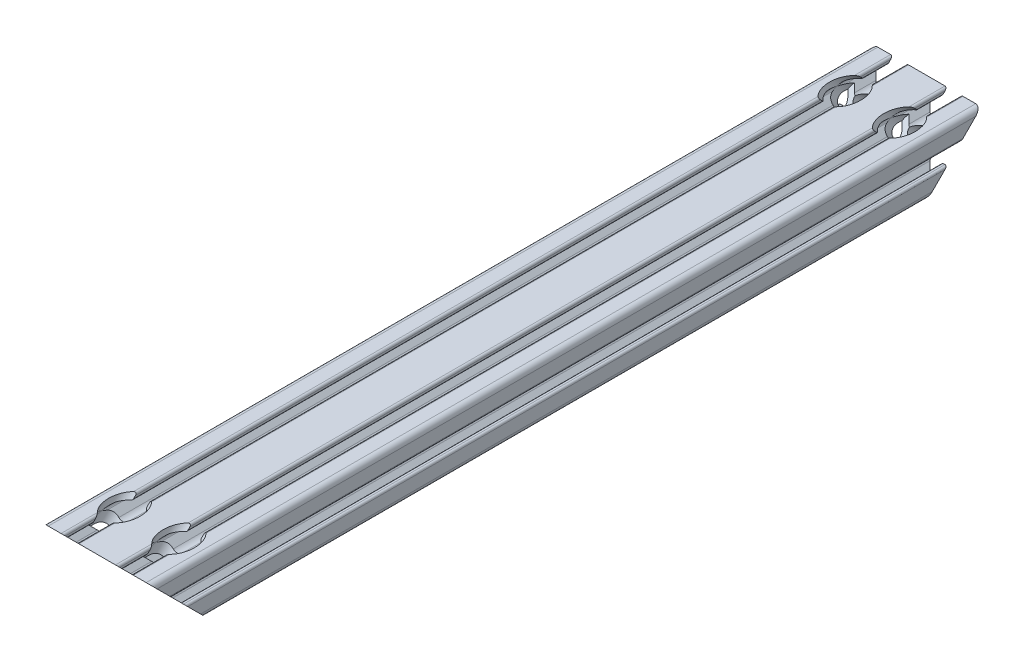
SolidWorks part; units mm, degrees
ref_plane "Front Plane" through (0, 0, 0) normal (0, 0, 1) x (1, 0, 0)
ref_plane "Top Plane" through (0, 0, 0) normal (0, 1, 0) x (1, 0, 0)
ref_plane "Right Plane" through (0, 0, 0) normal (1, 0, 0) x (0, 0, -1)
sketch "Sketch1" plane through (0, 0, 0) normal (0, 0, 1) x (1, 0, 0)
  line L2 (-19.9898, 7.9883) -> (-19.9898, 3.2893)
  line L3 (-17.9832, 9.9949) -> (-13.2842, 9.9949)
  line L4 (-12.4968, 9.2075) -> (-12.4968, 8.4963)
  line L5 (-12.8016, 8.1915) -> (-14.9098, 8.1915)
  line L6 (-15.5025, 6.7606) -> (-13.2477, 4.5058)
  line L7 (-16.7555, 5.5076) -> (-14.5007, 3.2528)
  line L8 (-18.1864, 4.9149) -> (-18.1864, 2.8067)
  line L9 (-18.4912, 2.5019) -> (-19.2024, 2.5019)
  line L11 (-11.1283, 3.6279) -> (-8.8615, 3.6279)
  line L12 (-13.6228, 1.1334) -> (-13.6228, -1.1334)
  line L13 (0, 9.9949) -> (-6.7056, 9.9949)
  line L14 (-7.493, 9.2075) -> (-7.493, 8.4963)
  line L15 (-7.1882, 8.1915) -> (-5.08, 8.1915)
  line L16 (-6.367, 1.1334) -> (-6.367, -1.1334)
  line L17 (-4.4873, 6.7606) -> (-6.7421, 4.5058)
  line L18 (-0.9396, 7.8023) -> (-5.4891, 3.2528)
  line L19 (-18.4912, -2.5019) -> (-19.2024, -2.5019)
  line L20 (-18.1864, -4.9149) -> (-18.1864, -2.8067)
  line L21 (-16.7555, -5.5076) -> (-14.5007, -3.2528)
  line L22 (-15.5025, -6.7606) -> (-13.2477, -4.5058)
  line L23 (-12.8016, -8.1915) -> (-14.9098, -8.1915)
  line L24 (-12.4968, -9.2075) -> (-12.4968, -8.4963)
  line L25 (-17.9832, -9.9949) -> (-13.2842, -9.9949)
  line L26 (-19.9898, -7.9883) -> (-19.9898, -3.2893)
  line L27 (0, -9.9949) -> (-6.7056, -9.9949)
  line L28 (-7.493, -9.2075) -> (-7.493, -8.4963)
  line L29 (-7.1882, -8.1915) -> (-5.08, -8.1915)
  line L30 (-4.4873, -6.7606) -> (-6.7421, -4.5058)
  line L31 (-0.9396, -7.8023) -> (-5.4891, -3.2528)
  line L32 (-11.1283, -3.6279) -> (-8.8615, -3.6279)
  line L34 (11.1283, -3.6279) -> (8.8615, -3.6279)
  line L35 (0.9396, -7.8023) -> (5.4891, -3.2528)
  line L36 (4.4873, -6.7606) -> (6.7421, -4.5058)
  line L37 (7.1882, -8.1915) -> (5.08, -8.1915)
  line L38 (7.493, -9.2075) -> (7.493, -8.4963)
  line L39 (0, -9.9949) -> (6.7056, -9.9949)
  line L40 (19.9898, -7.9883) -> (19.9898, -3.2893)
  line L41 (17.9832, -9.9949) -> (13.2842, -9.9949)
  line L42 (12.4968, -9.2075) -> (12.4968, -8.4963)
  line L43 (12.8016, -8.1915) -> (14.9098, -8.1915)
  line L44 (15.5025, -6.7606) -> (13.2477, -4.5058)
  line L45 (16.7555, -5.5076) -> (14.5007, -3.2528)
  line L46 (18.1864, -4.9149) -> (18.1864, -2.8067)
  line L47 (18.4912, -2.5019) -> (19.2024, -2.5019)
  line L48 (0.9396, 7.8023) -> (5.4891, 3.2528)
  line L49 (4.4873, 6.7606) -> (6.7421, 4.5058)
  line L50 (6.367, 1.1334) -> (6.367, -1.1334)
  line L51 (7.1882, 8.1915) -> (5.08, 8.1915)
  line L52 (7.493, 9.2075) -> (7.493, 8.4963)
  line L53 (0, 9.9949) -> (6.7056, 9.9949)
  line L54 (13.6228, 1.1334) -> (13.6228, -1.1334)
  line L55 (11.1283, 3.6279) -> (8.8615, 3.6279)
  line L56 (18.4912, 2.5019) -> (19.2024, 2.5019)
  line L57 (18.1864, 4.9149) -> (18.1864, 2.8067)
  line L58 (16.7555, 5.5076) -> (14.5007, 3.2528)
  line L59 (15.5025, 6.7606) -> (13.2477, 4.5058)
  line L60 (12.8016, 8.1915) -> (14.9098, 8.1915)
  line L61 (12.4968, 9.2075) -> (12.4968, 8.4963)
  line L62 (17.9832, 9.9949) -> (13.2842, 9.9949)
  line L63 (19.9898, 7.9883) -> (19.9898, 3.2893)
  circle A0 centre (-9.9949, 0) radius 2.1463
  arc A1 (-19.9898, 7.9883) -> (-17.9832, 9.9949) centre (-17.9832, 7.9883) cw
  arc A2 (-16.7555, 5.5076) -> (-18.1864, 4.9149) centre (-17.3482, 4.9149) ccw
  arc A3 (-14.9098, 8.1915) -> (-15.5025, 6.7606) centre (-14.9098, 7.3533) ccw
  arc A4 (-13.2842, 9.9949) -> (-12.4968, 9.2075) centre (-13.2842, 9.2075) cw
  arc A5 (-19.9898, 3.2893) -> (-19.2024, 2.5019) centre (-19.2024, 3.2893) ccw
  arc A6 (-18.1864, 2.8067) -> (-18.4912, 2.5019) centre (-18.4912, 2.8067) cw
  arc A7 (-12.4968, 8.4963) -> (-12.8016, 8.1915) centre (-12.8016, 8.4963) cw
  arc A8 (-11.1283, 3.6279) -> (-13.2477, 4.5058) centre (-11.1283, 6.6251) cw
  arc A9 (-13.6228, 1.1334) -> (-14.5007, 3.2528) centre (-16.62, 1.1334) ccw
  arc A10 (0.9396, 7.8023) -> (-0.9396, 7.8023) centre (0, 6.8627) ccw
  arc A11 (-0.9396, -7.8023) -> (0.9396, -7.8023) centre (0, -6.8627) ccw
  arc A12 (-6.7056, 9.9949) -> (-7.493, 9.2075) centre (-6.7056, 9.2075) ccw
  arc A13 (-7.493, 8.4963) -> (-7.1882, 8.1915) centre (-7.1882, 8.4963) ccw
  arc A14 (-8.8615, 3.6279) -> (-6.7421, 4.5058) centre (-8.8615, 6.6251) ccw
  arc A15 (-6.367, 1.1334) -> (-5.4891, 3.2528) centre (-3.3698, 1.1334) cw
  arc A16 (-5.08, 8.1915) -> (-4.4873, 6.7606) centre (-5.08, 7.3533) cw
  arc A17 (-13.6228, -1.1334) -> (-14.5007, -3.2528) centre (-16.62, -1.1334) cw
  arc A18 (-11.1283, -3.6279) -> (-13.2477, -4.5058) centre (-11.1283, -6.6251) ccw
  arc A19 (-12.4968, -8.4963) -> (-12.8016, -8.1915) centre (-12.8016, -8.4963) ccw
  arc A20 (-18.1864, -2.8067) -> (-18.4912, -2.5019) centre (-18.4912, -2.8067) ccw
  arc A21 (-19.9898, -3.2893) -> (-19.2024, -2.5019) centre (-19.2024, -3.2893) cw
  arc A22 (-13.2842, -9.9949) -> (-12.4968, -9.2075) centre (-13.2842, -9.2075) ccw
  arc A23 (-14.9098, -8.1915) -> (-15.5025, -6.7606) centre (-14.9098, -7.3533) cw
  arc A24 (-16.7555, -5.5076) -> (-18.1864, -4.9149) centre (-17.3482, -4.9149) cw
  arc A25 (-19.9898, -7.9883) -> (-17.9832, -9.9949) centre (-17.9832, -7.9883) ccw
  arc A26 (-5.08, -8.1915) -> (-4.4873, -6.7606) centre (-5.08, -7.3533) ccw
  arc A27 (-6.7056, -9.9949) -> (-7.493, -9.2075) centre (-6.7056, -9.2075) cw
  arc A28 (-7.493, -8.4963) -> (-7.1882, -8.1915) centre (-7.1882, -8.4963) cw
  arc A29 (-8.8615, -3.6279) -> (-6.7421, -4.5058) centre (-8.8615, -6.6251) cw
  arc A30 (-6.367, -1.1334) -> (-5.4891, -3.2528) centre (-3.3698, -1.1334) ccw
  arc A31 (6.367, -1.1334) -> (5.4891, -3.2528) centre (3.3698, -1.1334) cw
  arc A32 (8.8615, -3.6279) -> (6.7421, -4.5058) centre (8.8615, -6.6251) ccw
  arc A33 (7.493, -8.4963) -> (7.1882, -8.1915) centre (7.1882, -8.4963) ccw
  arc A34 (6.7056, -9.9949) -> (7.493, -9.2075) centre (6.7056, -9.2075) ccw
  arc A35 (5.08, -8.1915) -> (4.4873, -6.7606) centre (5.08, -7.3533) cw
  arc A36 (19.9898, -7.9883) -> (17.9832, -9.9949) centre (17.9832, -7.9883) cw
  arc A37 (16.7555, -5.5076) -> (18.1864, -4.9149) centre (17.3482, -4.9149) ccw
  arc A38 (14.9098, -8.1915) -> (15.5025, -6.7606) centre (14.9098, -7.3533) ccw
  arc A39 (13.2842, -9.9949) -> (12.4968, -9.2075) centre (13.2842, -9.2075) cw
  arc A40 (19.9898, -3.2893) -> (19.2024, -2.5019) centre (19.2024, -3.2893) ccw
  arc A41 (18.1864, -2.8067) -> (18.4912, -2.5019) centre (18.4912, -2.8067) cw
  arc A42 (12.4968, -8.4963) -> (12.8016, -8.1915) centre (12.8016, -8.4963) cw
  arc A43 (11.1283, -3.6279) -> (13.2477, -4.5058) centre (11.1283, -6.6251) cw
  arc A44 (13.6228, -1.1334) -> (14.5007, -3.2528) centre (16.62, -1.1334) ccw
  arc A45 (5.08, 8.1915) -> (4.4873, 6.7606) centre (5.08, 7.3533) ccw
  arc A46 (6.367, 1.1334) -> (5.4891, 3.2528) centre (3.3698, 1.1334) ccw
  arc A47 (8.8615, 3.6279) -> (6.7421, 4.5058) centre (8.8615, 6.6251) cw
  arc A48 (7.493, 8.4963) -> (7.1882, 8.1915) centre (7.1882, 8.4963) cw
  arc A49 (6.7056, 9.9949) -> (7.493, 9.2075) centre (6.7056, 9.2075) cw
  arc A50 (13.6228, 1.1334) -> (14.5007, 3.2528) centre (16.62, 1.1334) cw
  arc A51 (11.1283, 3.6279) -> (13.2477, 4.5058) centre (11.1283, 6.6251) ccw
  arc A52 (12.4968, 8.4963) -> (12.8016, 8.1915) centre (12.8016, 8.4963) ccw
  arc A53 (18.1864, 2.8067) -> (18.4912, 2.5019) centre (18.4912, 2.8067) ccw
  arc A54 (19.9898, 3.2893) -> (19.2024, 2.5019) centre (19.2024, 3.2893) cw
  arc A55 (13.2842, 9.9949) -> (12.4968, 9.2075) centre (13.2842, 9.2075) ccw
  arc A56 (14.9098, 8.1915) -> (15.5025, 6.7606) centre (14.9098, 7.3533) cw
  arc A57 (16.7555, 5.5076) -> (18.1864, 4.9149) centre (17.3482, 4.9149) cw
  arc A58 (19.9898, 7.9883) -> (17.9832, 9.9949) centre (17.9832, 7.9883) ccw
  circle A59 centre (9.9949, 0) radius 2.1463
  point P186 (9.9949, 3.6279)
extrude "Boss-Extrude1" add sketch "Sketch1" along normal mid plane 304.8
sketch "Sketch2" plane through (0, 0, 0) normal (1, 0, 0) x (0, 0, -1)
  line L0 (-152.4, 9.9949) -> (-152.4, -9.9949)
  line L1 (-152.4, -9.9949) -> (-132.4102, -9.9949)
  line L2 (-132.4102, -9.9949) -> (-152.4, 9.9949)
  line L3 (0, 0) -> (0, 9.9949) construction
  line L5 (-152.4, 9.9949) -> (152.4, 9.9949) construction
  line L6 (132.4102, -9.9949) -> (152.4, 9.9949)
  line L7 (152.4, -9.9949) -> (132.4102, -9.9949)
  line L8 (152.4, 9.9949) -> (152.4, -9.9949)
extrude "Cut-Extrude1" cut sketch "Sketch2" against normal through all and the other way through all
ref_plane "Plane1" through (-9.9949, 0, 0) normal (1, 0, 0) x (0, 0, -1)
sketch "Sketch3" plane through (-9.9949, 0, 0) normal (1, 0, 0) x (0, 0, -1)
  line L0 (-152.4, -9.9949) -> (-128.3443, 14.0608) construction
  line L1 (-132.4102, -9.9949) -> (-152.4, 9.9949) construction
  line L2 (-128.3443, 14.0608) -> (-132.4102, 18.1266)
  line L3 (-132.4102, 18.1266) -> (-142.5819, 7.955)
  line L4 (-142.5819, 7.955) -> (-140.3898, 5.7629)
  line L5 (-140.3898, 5.7629) -> (-144.2789, 1.8738)
  line L6 (-144.2789, 1.8738) -> (-142.4051, 0)
  line L7 (-124.2785, 9.9949) -> (-134.4501, -0.1768) construction
  line L8 (-144.5514, 2.1463) -> (-140.2588, -2.1463) construction
  line L9 (-152.4, 9.9949) -> (152.4, 9.9949) construction
  line L10 (-128.3443, 14.0608) -> (-142.4051, 0)
  dimension "D1" = 5.3
  dimension "D2" = 11.5
  dimension "D3" = 5.5
revolve "Cut-Revolve1" cut sketch "Sketch3" angle 360 mid plane about L0
mirror "Mirror1" about plane through (0, 0, 0) normal (0, 0, 1) of "Cut-Revolve1"
mirror "Mirror2" about plane through (0, 0, 0) normal (1, 0, 0) of "Cut-Revolve1", "Mirror1"
